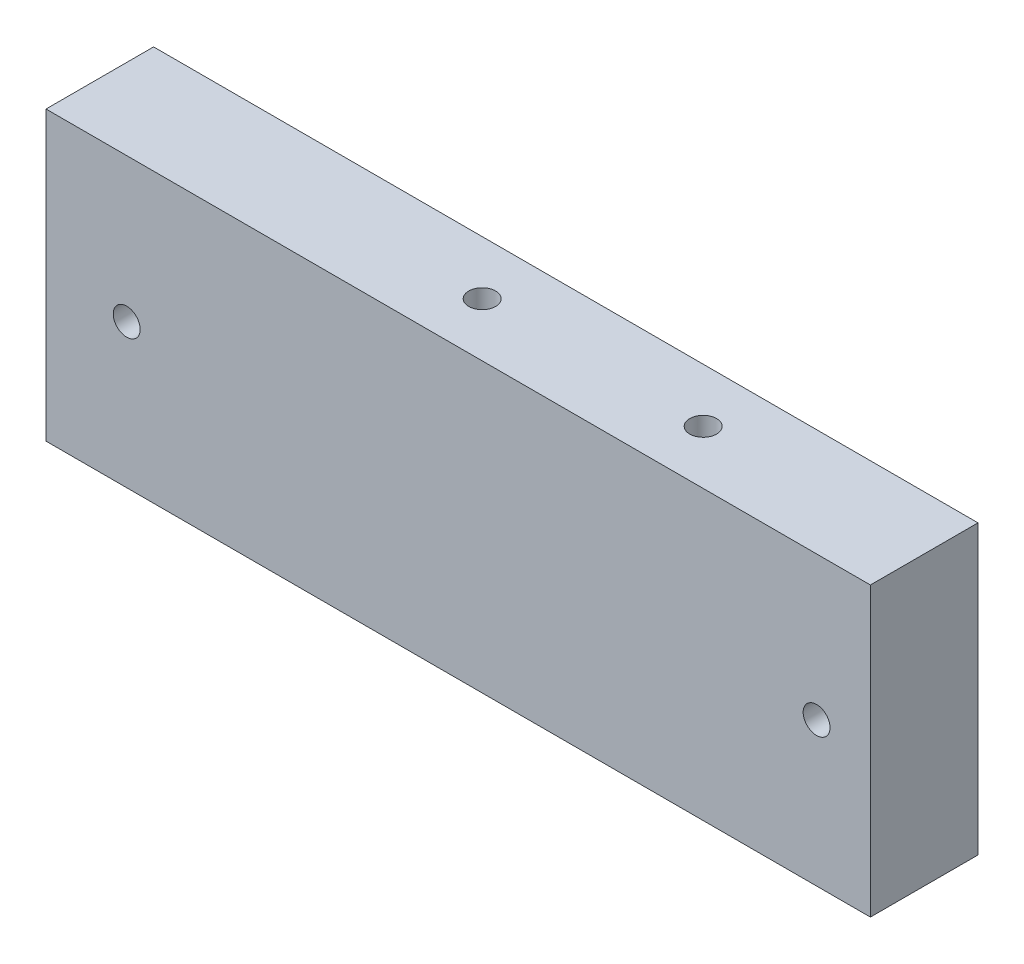
SolidWorks part; units mm, degrees
material "Beech"
ref_plane "Front Plane" through (0, 0, 0) normal (0, 0, 1) x (1, 0, 0)
ref_plane "Top Plane" through (0, 0, 0) normal (0, 1, 0) x (1, 0, 0)
ref_plane "Right Plane" through (0, 0, 0) normal (1, 0, 0) x (0, 0, -1)
sketch "Sketch1" plane through (0, 0, 0) normal (0, 0, 1) x (1, 0, 0)
  line L0 (-244.0045, -53) -> (-244.0045, -19) construction
  line L1 (-341.3045, -19.05) -> (-244.0045, -19.05)
  line L2 (-341.3045, -19.05) -> (-341.3045, -53)
  line L3 (-341.3045, -53) -> (-244.0045, -53)
  line L4 (-244.0045, -19.05) -> (-244.0045, -53)
  dimension "D2" = 33.95
extrude "Boss-Extrude1" add sketch "Sketch1" against normal blind 12.7
hole_wizard "Hole1" positions "Sketch2" profile "Sketch3" legacy
sketch "Sketch2" plane through (-124.0045, 0, -10.4243) normal (0, 1, 0) x (-1, 0, 0)
  line L21 (0, 109.0243) -> (0, 155.0243) construction
  point P37 (126.35, 161.3743)
  point P42 (146.0833, 4.0743)
  point P44 (172.1667, 4.0743)
  point P63 (126.35, 34.5243)
  point P65 (126.35, 130.9243)
  point P76 (-172.1667, 4.0743)
  point P77 (-146.0833, 4.0743)
  point P78 (-126.35, 34.5243)
  point P79 (-126.35, 130.9243)
  point P80 (-126.35, 161.3743)
sketch "Sketch3" plane through (-250.3545, 0, 150.95) normal (1, 0, 0) x (0, 0, 1)
  line L0 (0, 0) -> (0, 32.7039)
  line L1 (0, 32.7039) -> (1.5875, 31.75)
  line L2 (1.5875, 31.75) -> (1.5875, 4.0177)
  line L3 (1.5875, 4.0177) -> (5.08, 0)
  line L4 (5.08, 0) -> (0, 0)
  line L5 (0, -14.3089) -> (0, 102.4216) construction
  line L6 (0, 32.7039) -> (-1.5875, 31.75) construction
  line L7 (-1.5875, 4.0177) -> (-5.08, 0) construction
  dimension "Diameter" = 3.175
  dimension "Depth" = 31.75
  dimension "C-Sink Diameter" = 10.16
  dimension "C-Sink Angle" = 82
  dimension "Drill Angle" = 118
hole_wizard "Hole2" positions "Sketch4" profile "Sketch5" legacy
sketch "Sketch4" plane through (-124.0045, -72.05, -10.4243) normal (0, -1, 0) x (1, 0, 0)
  line L21 (0, 109.0243) -> (0, 155.0243) construction
  point P37 (126.35, 161.3743)
  point P42 (146.0833, 4.0743)
  point P44 (172.1667, 4.0743)
  point P63 (126.35, 34.5243)
  point P65 (126.35, 130.9243)
  point P76 (-172.1667, 4.0743)
  point P77 (-146.0833, 4.0743)
  point P78 (-126.35, 34.5243)
  point P79 (-126.35, 130.9243)
  point P80 (-126.35, 161.3743)
sketch "Sketch5" plane through (2.3455, -72.05, 150.95) normal (1, 0, 0) x (0, 0, -1)
  line L0 (0, 0) -> (0, 32.7039)
  line L1 (0, 32.7039) -> (1.5875, 31.75)
  line L2 (1.5875, 31.75) -> (1.5875, 4.0177)
  line L3 (1.5875, 4.0177) -> (5.08, 0)
  line L4 (5.08, 0) -> (0, 0)
  line L5 (0, -14.3089) -> (0, 102.4216) construction
  line L6 (0, 32.7039) -> (-1.5875, 31.75) construction
  line L7 (-1.5875, 4.0177) -> (-5.08, 0) construction
  dimension "Diameter" = 3.175
  dimension "Depth" = 31.75
  dimension "C-Sink Diameter" = 10.16
  dimension "C-Sink Angle" = 82
  dimension "Drill Angle" = 118
hole_wizard "Hole5" positions "Sketch8" profile "Sketch9" legacy
sketch "Sketch8" plane through (-124.0045, -208.2867, -12.7) normal (0, 0, -1) x (-1, 0, 0)
  line L0 (120, 172.2617) -> (217.3, 172.2617) construction
  point P8 (126.35, 172.2617)
  point P10 (207.775, 172.2617)
sketch "Sketch9" plane through (-331.7795, -36.025, -12.7) normal (1, 0, 0) x (0, 1, 0)
  line L0 (0, 0) -> (0, 32.7039)
  line L1 (0, 32.7039) -> (1.5875, 31.75)
  line L2 (1.5875, 31.75) -> (1.5875, 4.0177)
  line L3 (1.5875, 4.0177) -> (5.08, 0)
  line L4 (5.08, 0) -> (0, 0)
  line L5 (0, -14.3089) -> (0, 102.4216) construction
  line L6 (0, 32.7039) -> (-1.5875, 31.75) construction
  line L7 (-1.5875, 4.0177) -> (-5.08, 0) construction
  dimension "Diameter" = 3.175
  dimension "Depth" = 31.75
  dimension "C-Sink Diameter" = 10.16
  dimension "C-Sink Angle" = 82
  dimension "Drill Angle" = 118
hole_wizard "Hole6" positions "Sketch10" profile "Sketch11" legacy
sketch "Sketch10" plane through (-124.0045, -6.35, -10.4243) normal (0, 1, 0) x (-1, 0, 0)
  line L12 (0, 0) -> (0, 155.0243) construction
  point P0 (-207.775, 333.0214)
  point P3 (-207.775, 225.489)
  point P6 (-207.775, 137.4243)
  point P9 (-172.1667, 4.0743)
  point P12 (-146.0833, 4.0743)
  point P15 (-94.6, 161.3743)
  point P18 (0, 161.3743)
  point P21 (94.6, 161.3743)
  point P24 (146.0833, 4.0743)
  point P27 (172.1667, 4.0743)
  point P30 (207.775, 137.4243)
  point P33 (207.775, 225.489)
  point P36 (207.775, 333.0214)
  point P39 (166.7958, 301.9704)
  point P42 (40.9792, 301.9704)
  point P45 (-40.9792, 301.9704)
  point P48 (-166.7958, 301.9704)
  point P51 (0, 193.1243)
  point P54 (0, 301.9704)
  point P57 (0, 412.3664)
  point P80 (-126.35, 106.8243)
  point P82 (-126.35, 58.6243)
  point P96 (126.35, 58.6243)
  point P97 (126.35, 106.8243)
sketch "Sketch11" plane through (83.7705, -6.35, 322.5971) normal (1, 0, 0) x (0, 0, 1)
  line L0 (0, 0) -> (0, 32.7039)
  line L1 (0, 32.7039) -> (1.5875, 31.75)
  line L2 (1.5875, 31.75) -> (1.5875, 4.0177)
  line L3 (1.5875, 4.0177) -> (5.08, 0)
  line L4 (5.08, 0) -> (0, 0)
  line L5 (0, -14.3089) -> (0, 102.4216) construction
  line L6 (0, 32.7039) -> (-1.5875, 31.75) construction
  line L7 (-1.5875, 4.0177) -> (-5.08, 0) construction
  dimension "Diameter" = 3.175
  dimension "Depth" = 31.75
  dimension "C-Sink Diameter" = 10.16
  dimension "C-Sink Angle" = 82
  dimension "Drill Angle" = 118
